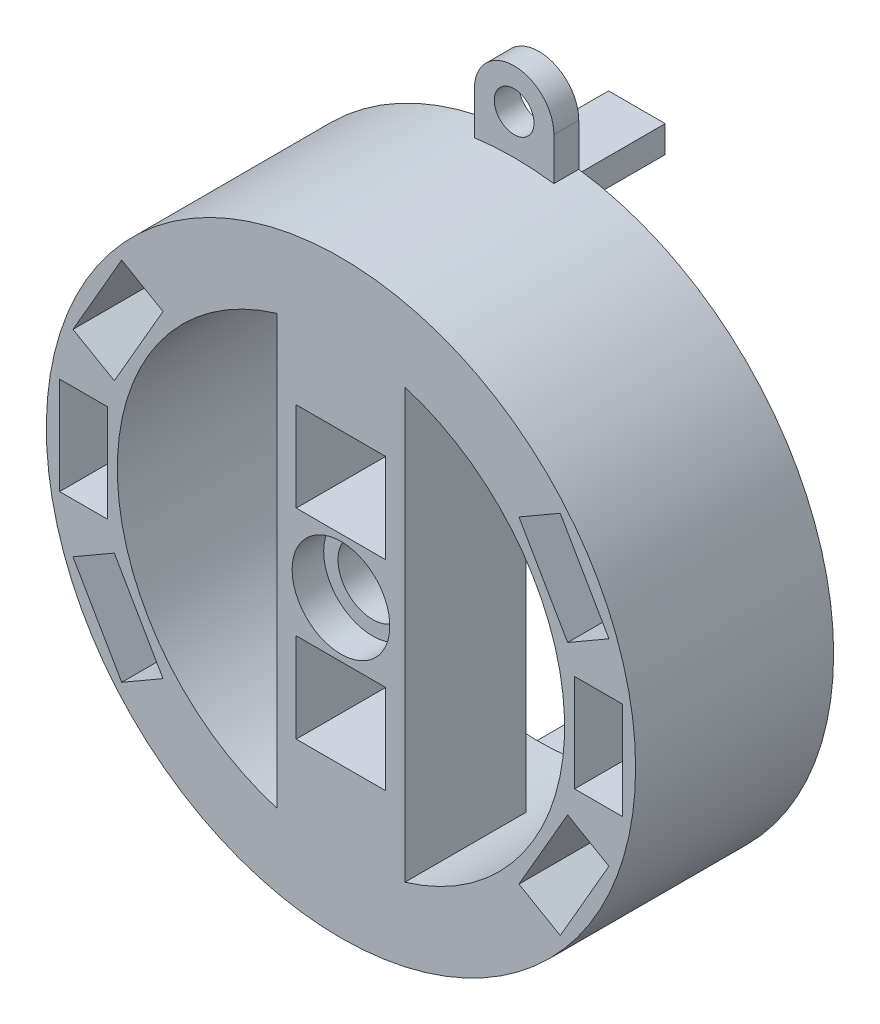
SolidWorks part; units mm, degrees
ref_plane "Front Plane" through (0, 0, 0) normal (0, 0, 1) x (1, 0, 0)
ref_plane "Top Plane" through (0, 0, 0) normal (0, 1, 0) x (1, 0, 0)
ref_plane "Right Plane" through (0, 0, 0) normal (1, 0, 0) x (0, 0, -1)
sketch "Sketch1" plane through (0, 0, 0) normal (0, 0, 1) x (1, 0, 0)
  line L0 (23.5, 0) -> (22.5, 0)
  line L1 (0, 25.15) -> (0, 22.5)
  line L3 (0, -22.5) -> (0, -29.64)
  line L4 (22.5, 0) -> (-22.5, 0)
  line L8 (28.3, 4.9) -> (23.5, 4.9)
  line L9 (28.3, 4.9) -> (28.3, -4.9)
  line L10 (28.3, -4.9) -> (23.5, -4.9)
  line L11 (23.5, 4.9) -> (23.5, -4.9)
  line L24 (-2.85, 27.85) -> (-2.85, 25.15)
  line L25 (-2.85, 27.85) -> (2.85, 27.85)
  line L26 (2.85, 27.85) -> (2.85, 25.15)
  line L27 (-2.85, 25.15) -> (2.85, 25.15)
  circle A0 centre (0, 0) radius 22.5
  circle A1 centre (0, 0) radius 29.64
  point P0 (0, 25.15)
  point P1 (23.5, 0)
  dimension "D3" = 5.7
  dimension "D1" = 1
  dimension "D2" = 2.65
  dimension "D4" = 2.7
extrude "Boss-Extrude1" add sketch "Sketch1" along normal blind 19.92 contours A1 L11 L8 L9 L10 L27 L24 L25 L26 A0 | L24 L27 L26 L25 | L8 L11 L10 L9 | L3 A1 L9 L10 L11 L0 A0 region at (-20.3658, 20.3658, 0) region at (0, 26.5, 0) region at (25.9, 0, 0)
extrude "Boss-Extrude2" add sketch "Sketch1<4>" against normal blind 9.85 contours L25 L26 L27 L24
sketch "Sketch1<4>" plane through (0, 0, 0) normal (0, 0, 1) x (1, 0, 0) same geometry as "Sketch1"
sketch "Sketch3" plane through (0, 0, 0) normal (0, 1, 0) x (1, 0, 0)
  line L0 (0, -26.5014) -> (0, 0)
pattern_circular "CirPattern2" count 2 over 360 about axis through (0, 0, 26.5014) along (0, 0, -1) of "Boss-Extrude2" reverse direction yes
sketch "Sketch4" plane through (0, 0, 19.92) normal (0, 0, 1) x (1, 0, 0)
  line L1 (6.4367, -24.2141) -> (-6.4367, -24.2141)
  line L2 (6.4367, -24.2141) -> (6.4367, 24.2141)
  line L3 (6.4367, 24.2141) -> (-6.4367, 24.2141)
  line L4 (-6.4367, -24.2141) -> (-6.4367, 24.2141)
  line L5 (6.4367, -24.2141) -> (-6.4367, 24.2141) construction
  line L6 (6.4367, 24.2141) -> (-6.4367, -24.2141) construction
  line L7 (-24.2141, 6.4367) -> (24.2141, 6.4367)
  line L8 (-24.2141, 6.4367) -> (-24.2141, -6.4367)
  line L9 (-24.2141, -6.4367) -> (24.2141, -6.4367)
  line L10 (24.2141, 6.4367) -> (24.2141, -6.4367)
  line L11 (-24.2141, 6.4367) -> (24.2141, -6.4367) construction
  line L12 (-24.2141, -6.4367) -> (24.2141, 6.4367) construction
  point P0 (0, 0)
  point P5 (0, 0)
extrude "Boss-Extrude3" add sketch "Sketch4" against normal blind 3.175 contours L2 L3 L4 L1
sketch "Sketch7" plane through (0, 0, 19.92) normal (0, 0, 1) x (1, 0, 0)
  circle A0 centre (0, 0) radius 4.9125
extrude "Cut-Extrude2" cut sketch "Sketch7" against normal up to next and the other way through all
sketch "Sketch8" plane through (0, 0, 16.745) normal (0, 0, 1) x (1, 0, 0)
  line L0 (0, -3.475) -> (0, -24.0864)
  line L5 (6.4367, 24.0864) -> (-6.4367, 24.0864)
  line L6 (6.4367, 24.0864) -> (6.4367, -24.0864)
  line L11 (6.4367, -24.0864) -> (-6.4367, -24.0864)
  line L12 (-6.4367, 24.0864) -> (-6.4367, -24.0864)
  line L13 (6.4367, 24.0864) -> (-6.4367, -24.0864) construction
  line L14 (6.4367, -24.0864) -> (-6.4367, 24.0864) construction
  circle A1 centre (0, 0) radius 3.475
  point P0 (0, 0)
  dimension "D2" = 12.8734
extrude "Boss-Extrude4" add sketch "Sketch8" against normal blind 9 contours L5 L12 L11 L6 | A1
extrude "Cut-Extrude1" cut sketch "Sketch1<3>" along normal blind 20 contours L8 L11 L10 L9 region at (25.9, 0, 0)
sketch "Sketch1<3>" plane through (0, 0, 0) normal (0, 0, 1) x (1, 0, 0) same geometry as "Sketch1"
pattern_circular "CirPattern1" count 2 every 30 about axis through (0, 0, 26.5014) along (0, 0, -1) of "Cut-Extrude1" reverse direction yes other way count 2
sketch "Sketch11" plane through (0, 0, 19.92) normal (0, 0, -1) x (-1, 0, 0)
  line L0 (0, 5.5625) -> (0, 4.9125)
  line L1 (-4.5, 14.5625) -> (4.5, 14.5625)
  line L2 (-4.5, 14.5625) -> (-4.5, 5.5625)
  line L3 (-4.5, 5.5625) -> (4.5, 5.5625)
  line L4 (4.5, 14.5625) -> (4.5, 5.5625)
  line L5 (-4.5, 14.5625) -> (4.5, 5.5625) construction
  line L6 (-4.5, 5.5625) -> (4.5, 14.5625) construction
  circle A0 centre (0, 0) radius 4.9125 construction
  point P0 (0, 10.0625)
  dimension "D1" = 9
extrude "Cut-Extrude21" cut sketch "Sketch11" along normal blind 29 contours L1 L4 L3 L2 region at (0, 10.0625, 19.92)
mirror "Mirror1" about plane through (0, 0, 0) normal (0, 1, 0) of "Cut-Extrude21"
sketch "Sketch12" plane through (0, 0, 0) normal (0, 0, -1) x (-1, 0, 0)
  line L0 (0, 31.64) -> (0, 29.64)
  line L1 (-4, 29.3689) -> (4, 29.3689)
  line L2 (-4, 29.3689) -> (-4, 33.64)
  line L3 (-4, 33.64) -> (4, 33.64)
  line L4 (4, 29.3689) -> (4, 33.64)
  circle A0 centre (0, 0) radius 29.64 construction
  circle A1 centre (0, 33.64) radius 2
  arc A2 (-4, 33.64) -> (4, 33.64) centre (0, 33.64) cw
  point P7 (0, 29.3689)
  circle M28 centre (0, 0) radius 29.64
  dimension "D2" = 4
  dimension "D1" = 2
extrude "Boss-Extrude5" add sketch "Sketch12" against normal blind 2.5 contours A1 L3 L2 L0 M28 | A2 L3 A1 | A1 L0 L4 L3 M28 region at (-2.3009, 31.3096, 0) region at (2.3009, 31.3096, 0) region at (0, 35.7294, 0)
mirror "Mirror2" about plane through (0, 0, 0) normal (0, 1, 0) of "Boss-Extrude5"
mirror "Mirror3" about plane through (0, 0, 0) normal (1, 0, 0) of "CirPattern1"
